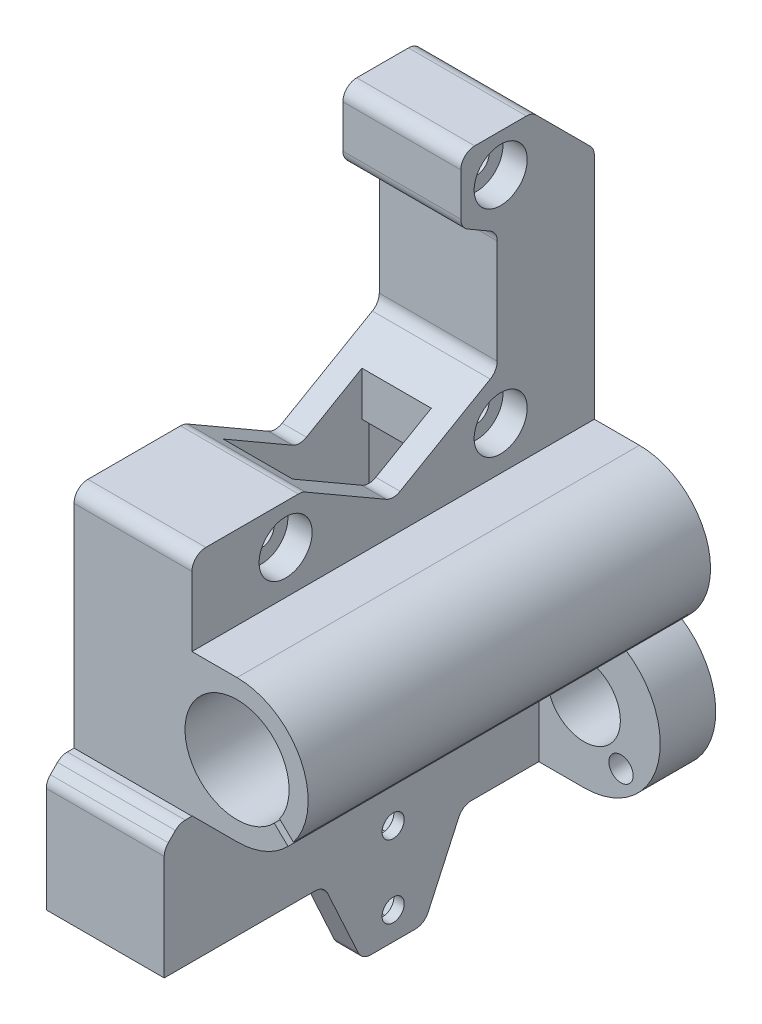
SolidWorks part; units mm, degrees
ref_plane "Front Plane" through (0, 0, 0) normal (0, 0, 1) x (1, 0, 0)
ref_plane "Top Plane" through (0, 0, 0) normal (0, 1, 0) x (1, 0, 0)
ref_plane "Right Plane" through (0, 0, 0) normal (1, 0, 0) x (0, 0, -1)
ref_plane "Plane1" through (50, 0, 0) normal (1, 0, 0) x (0, 0, -1)
sketch "Sketch1" plane through (50, 0, 0) normal (1, 0, 0) x (0, 0, -1)
  line L0 (-62, -12.5) -> (-59.8, -10.3)
  line L1 (-62, -28.5) -> (0, -28.5)
  line L2 (-62, -28.5) -> (-62, -12.5)
  line L3 (-19.244, 53) -> (-8.9612, 53)
  line L4 (0, -28.5) -> (0, 44.0388)
  line L5 (-59.8, -10.3) -> (-58, -10.3)
  line L6 (-58, -10.3) -> (-58, 22.2516)
  line L9 (-58, 22.2516) -> (-42.1152, 22.2516)
  line L10 (-8.9612, 53) -> (0, 44.0388)
  line L11 (-19.244, 53) -> (-19.244, 43.6879)
  line L13 (-29, 14.6795) -> (-14, 23.3397)
  line L14 (-14, 23.3397) -> (-14, 40.6603)
  line L15 (-14, 40.6603) -> (-19.244, 43.6879)
  line L18 (-42.1152, 22.2516) -> (-29, 14.6795)
  line L19 (-42, -12.5) -> (-16, -12.5)
  line L20 (-42, -12.5) -> (-42, -11)
  line L21 (-42, -11) -> (-16, -11)
  line L22 (-16, -12.5) -> (-16, -11)
  line L23 (-38.5473, 43.8084) -> (-46.1398, 39.4248) [skipped]
  line L24 (-44, 29.636) -> (-44, 20.8689) [skipped]
  circle A0 centre (-44.5, 16.5) radius 1.825
  circle A1 centre (-29, 32) radius 15 construction
  circle A2 centre (-13.5, 16.5) radius 1.825
  circle A3 centre (-13.5, 47.5) radius 1.825
  point P21 (-29, -11)
  dimension "D3" = 3.65
  dimension "D4" = 30
  dimension "D1" = 31
  dimension "D2" = 31
  dimension "D5" = 1.5
  dimension "D6" = 16
  dimension "D7" = 26
  dimension "D8" = 29
  dimension "D9" = 21
  dimension "D10" = 15.5
  dimension "D11" = 15.5
extrude "Boss-Extrude1" add sketch "Sketch1" along normal blind 17 separate body
sketch "Sketch8" plane through (0, 0, 58) normal (0, 0, 1) x (1, 0, 0)
  line L0 (67, -28.5) -> (50, -28.5) construction
  line L3 (67, 22.2516) -> (67, -10.3) construction
  line L4 (73.5, 10.25) -> (67, 10.25)
  line L5 (67, 10.25) -> (67, -10.25)
  line L6 (67, -10.25) -> (73.5, -10.25)
  line L7 (67, 10.25) -> (67, -10.25)
  arc A3 (73.5, -10.25) -> (73.5, 10.25) centre (73.5, 0) ccw
  line M3 (67, -10.3) -> (67, 22.2516)
  dimension "D1" = 6.5
  dimension "D2" = 28.5
  dimension "D3" = 10.25
extrude "Boss-Extrude2" add sketch "Sketch8" against normal up to surface (58 mm away) contours L6 A3 L4 M3 region at (74.455, 0, 58) up to face at (58.5, 7.7694, 0)
sketch "Sketch17" plane through (67, 0, 0) normal (1, 0, 0) x (0, 0, -1)
  line L0 (-33.5, -40.5) -> (-39, -28.5)
  line L1 (-62, -28.5) -> (0, -28.5) construction
  line L2 (-39, -28.5) -> (-19, -28.5)
  line L3 (-19, -28.5) -> (-24.5, -40.5)
  line L4 (-24.5, -40.5) -> (-33.5, -40.5)
  line L5 (-62, -28.5) -> (0, -28.5) construction
  line L6 (0, -28.5) -> (0, -10.25) construction
  point P10 (-29, -28.5)
  dimension "D1" = 9
  dimension "D2" = 12
  dimension "D3" = 20
  dimension "D4" = 29
extrude "Boss-Extrude4" add sketch "Sketch17" against normal blind 3.5
sketch "Sketch9" plane through (0, 0, 58) normal (0, 0, 1) x (1, 0, 0)
  circle A0 centre (73.5, 0) radius 7.5
  dimension "D1" = 15
extrude "Cut-Extrude5" cut sketch "Sketch9" against normal blind 61
sketch "Sketch18" plane through (67, 0, 0) normal (1, 0, 0) x (0, 0, -1)
  line L0 (-33.5, -40.5) -> (-24.5, -40.5) construction
  line L1 (-33.5, -40.5) -> (-24.5, -40.5) construction
  line L2 (-29, -40.5) -> (-29, -26) construction
  circle A0 centre (-29, -36.5) radius 1.6
  circle A2 centre (-29, -26) radius 1.6
  dimension "D3" = 3.2
  dimension "D1" = 10.5
  dimension "D2" = 4
extrude "Cut-Extrude12" cut sketch "Sketch18" against normal blind 5.5
sketch "Sketch19" plane through (67, 0, 0) normal (-1, 0, 0) x (0, 0, 1)
  line L1 (30.7609, -33.45) -> (27.2391, -33.45)
  line L2 (27.2391, -33.45) -> (25.4782, -36.5)
  line L3 (25.4782, -36.5) -> (27.2391, -39.55)
  line L4 (27.2391, -39.55) -> (30.7609, -39.55)
  line L5 (30.7609, -39.55) -> (32.5218, -36.5)
  line L6 (32.5218, -36.5) -> (30.7609, -33.45)
  line L7 (32.5218, -26) -> (30.7609, -22.95)
  line L8 (30.7609, -22.95) -> (27.2391, -22.95)
  line L9 (27.2391, -22.95) -> (25.4782, -26)
  line L10 (25.4782, -26) -> (27.2391, -29.05)
  line L11 (27.2391, -29.05) -> (30.7609, -29.05)
  line L12 (30.7609, -29.05) -> (32.5218, -26)
  circle A0 centre (29, -36.5) radius 3.05 construction
  circle A1 centre (29, -26) radius 3.05 construction
  dimension "D1" = 6.1
extrude "Cut-Extrude13" cut sketch "Sketch19" along normal blind 3.5 from offset 1.5
fillet "Fillet1" radius 2 15 edges at (58.5, 22.2516, 42.1152) (58.5, 44.0388, 0) (58.5, 53, 8.9612) (58.5, 53, 19.244) (58.5, 43.6879, 19.244) (58.5, 14.6795, 29) (58.5, 23.3397, 14) (58.5, 40.6603, 14) (58.5, -10.3, 59.8) (65.25, -40.5, 24.5) (65.25, -28.5, 19) (65.25, -28.5, 39) (65.25, -40.5, 33.5) (58.5, 22.2516, 58) (58.5, -12.5, 62)
sketch "Sketch3" plane through (0, 22.2516, 0) normal (0, 1, 0) x (1, 0, 0)
  line L1 (53.5, -40) -> (63.5, -40)
  line L2 (53.5, -40) -> (53.5, -20)
  line L3 (53.5, -20) -> (63.5, -20)
  line L4 (63.5, -40) -> (63.5, -20)
  line L5 (50, -55) -> (50, 55) construction
  line L6 (67, 0) -> (67, -58) construction
  line L7 (67, 0) -> (50, 0) construction
  dimension "D1" = 3.5
  dimension "D2" = 3.5
  dimension "D3" = 20
  dimension "D5" = 20
extrude "Cut-Extrude1" cut sketch "Sketch3" against normal blind 13
sketch "Sketch4" plane through (0, -28.5, 0) normal (0, -1, 0) x (1, 0, 0)
  line L0 (50, -55) -> (50, 55) construction
  line L1 (67, 0) -> (50, 0) construction
  line L15 (53.5, 19) -> (56.5711, 16)
  line L16 (56.5711, 16) -> (60.5, 16)
  line L17 (60.5, 16) -> (63.5, 19.0711)
  line L18 (63.5, 19.0711) -> (63.5, 36)
  line L19 (63.5, 36) -> (61.4548, 42)
  line L20 (61.4548, 42) -> (55.5452, 42)
  line L21 (55.5452, 42) -> (53.5, 36)
  line L22 (53.5, 36) -> (53.5, 19)
  line L23 (67, 62) -> (67, 40.2834) construction
  point P2 (58.5356, 16)
  dimension "D1" = 3.5
  dimension "D2" = 3.5
  dimension "D3" = 6
  dimension "D4" = 16
  dimension "D5" = 26
  dimension "D6" = 3
extrude "Cut-Extrude2" cut sketch "Sketch4" against normal blind 42
sketch "Sketch5" plane through (67, 0, 0) normal (1, 0, 0) x (0, 0, -1)
  circle A0 centre (-13.5, 16.5) radius 3.825
  circle A1 centre (-44.5, 16.5) radius 3.825
  circle A2 centre (-13.5, 47.5) radius 0.0001
  circle A3 centre (-13.5, 47.5) radius 3.825
  dimension "D1" = 7.65
extrude "Cut-Extrude3" cut sketch "Sketch5" against normal blind 3.5
sketch "Sketch7" plane through (0, -28.5, 0) normal (0, -1, 0) x (1, 0, 0)
  line L0 (56.7517, 54.6809) -> (57.1299, 55.738)
  line L1 (57.1299, 55.738) -> (59.92, 55.738)
  line L2 (59.92, 55.738) -> (60.2691, 54.6709)
  line L3 (67, 0) -> (50, 0) construction
  line L4 (50, 62) -> (50, 0) construction
  line L5 (56.7517, 9.6809) -> (57.1299, 10.738)
  line L6 (57.1299, 10.738) -> (59.92, 10.738)
  line L7 (59.92, 10.738) -> (60.2691, 9.6709)
  line L8 (67, 17.7166) -> (67, 0) construction
  arc A0 (56.7517, 54.6809) -> (60.2691, 54.6709) centre (58.5, 51) ccw
  arc A2 (56.7517, 9.6809) -> (60.2691, 9.6709) centre (58.5, 6) ccw
  dimension "D2" = 4.075
  dimension "D1" = 17
  dimension "D3" = 6
  dimension "D4" = 45
  dimension "D5" = 8.5
extrude "Cut-Extrude4" cut sketch "Sketch7" against normal blind 38
sketch "Sketch11" plane through (0, 0, 0) normal (0, 0, -1) x (-1, 0, 0)
  line L0 (-67, -28.5) -> (-50, -28.5) construction
  line L1 (-73.5, -28.5) -> (-67, -28.5)
  line L2 (-73.5, -17.5) -> (-83.3811, -28.233) construction
  line L4 (-67, -28.5) -> (-67, -7.7324)
  line L5 (-78.5591, -7.7324) -> (-67, -7.7324)
  arc A0 (-78.5591, -7.7324) -> (-73.5, -28.5) centre (-73.5, -17.5) ccw
  circle A1 centre (-73.5, -17.5) radius 5.25
  circle A3 centre (-73.5, -17.5) radius 8 construction
  point P2 (-73.5, 0)
  dimension "D1" = 22
  dimension "D2" = 10.5
  dimension "D3" = 16
  dimension "D4" = 6.5
extrude "Boss-Extrude3" add sketch "Sketch11" against normal blind 8
sketch "Sketch10" plane through (0, 0, 58) normal (0, 0, 1) x (1, 0, 0)
  line L0 (81.0723, -7.3532) -> (78.4403, -4.8406)
  line L1 (79.2798, -3.983) -> (81.8576, -6.4439)
  line L2 (81.0723, -7.3532) -> (81.8576, -6.4439)
  line L3 (79.2798, -3.983) -> (78.4403, -4.8406)
  dimension "D1" = 1.2
extrude "Cut-Extrude6" cut sketch "Sketch10" against normal blind 57
sketch "Sketch12" plane through (0, 0, 0) normal (0, 0, -1) x (-1, 0, 0)
  line L0 (-73.5043, -17.5048) -> (-68.8655, -12.3295) construction
  circle A1 centre (-73.5, -17.5) radius 8 construction
  circle A2 centre (-68.1603, -11.5428) radius 1.75
  circle A3 centre (-78.8397, -23.4572) radius 1.75
  point P5 (-73.5, -17.5)
  dimension "D1" = 16
  dimension "D2" = 3.5
extrude "Cut-Extrude9" cut sketch "Sketch12" against normal blind 10
sketch "Sketch13" plane through (0, 0, 8) normal (0, 0, 1) x (1, 0, 0)
  line L1 (82.3899, -23.5133) -> (80.6634, -20.4106)
  line L2 (80.6634, -20.4106) -> (77.1131, -20.3545)
  line L3 (77.1131, -20.3545) -> (75.2894, -23.401)
  line L4 (75.2894, -23.401) -> (77.0159, -26.5037)
  line L5 (77.0159, -26.5037) -> (80.5662, -26.5599)
  line L6 (80.5662, -26.5599) -> (82.3899, -23.5133)
  line L7 (67.3519, -15.0003) -> (70.7503, -13.9717)
  line L8 (70.7503, -13.9717) -> (71.5588, -10.5143)
  line L9 (71.5588, -10.5143) -> (68.9688, -8.0854)
  line L10 (68.9688, -8.0854) -> (65.5703, -9.1139)
  line L11 (65.5703, -9.1139) -> (64.7619, -12.5714)
  line L12 (64.7619, -12.5714) -> (67.3519, -15.0003)
  circle A0 centre (78.8397, -23.4572) radius 3.075 construction
  circle A1 centre (68.1603, -11.5428) radius 3.075 construction
  dimension "D1" = 6.15
extrude "Cut-Extrude10" cut sketch "Sketch13" along normal blind 3
sketch "Sketch20" plane through (0, 9.5, 0) normal (0, -1, 0) x (1, 0, 0)
  circle A0 centre (58.5, 6) radius 4.738
  circle A1 centre (58.5, 51) radius 4.738
extrude "Cut-Extrude14" cut sketch "Sketch20" along normal blind 5
